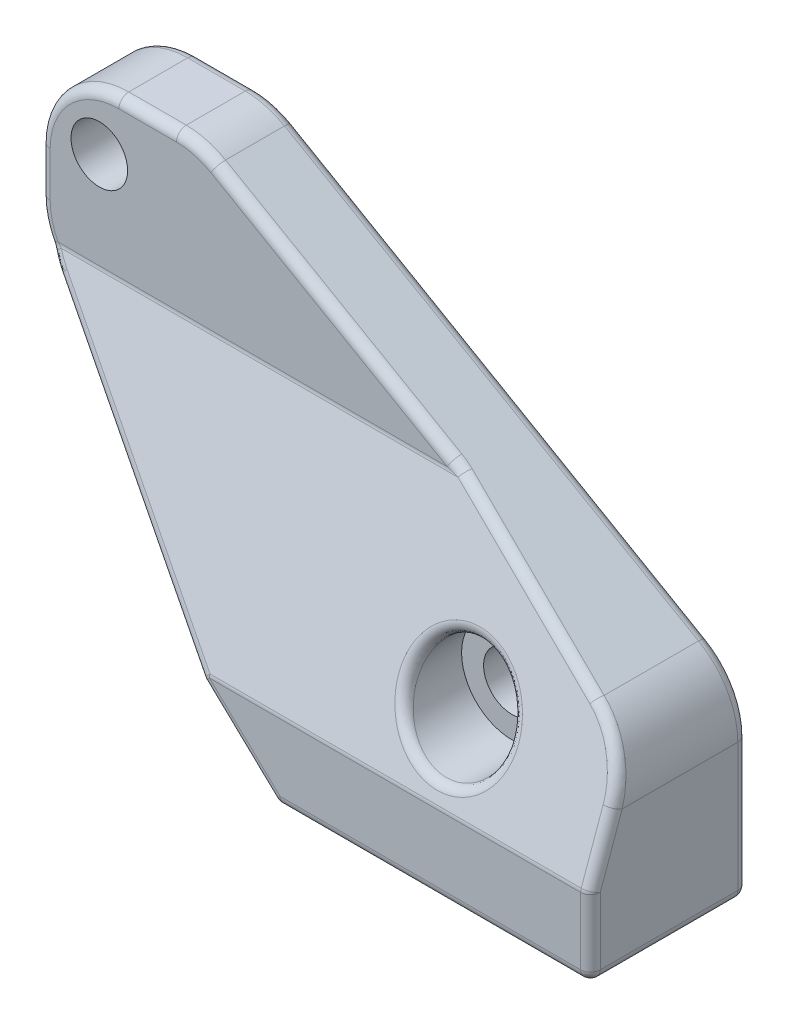
SolidWorks part; units mm, degrees
ref_plane "Front Plane" through (0, 0, 0) normal (0, 0, 1) x (1, 0, 0)
ref_plane "Top Plane" through (0, 0, 0) normal (0, 1, 0) x (1, 0, 0)
ref_plane "Right Plane" through (0, 0, 0) normal (1, 0, 0) x (0, 0, -1)
sketch "Sketch8" plane through (0, 0, 0) normal (0, 0, 1) x (1, 0, 0)
  line L0 (0, 0) -> (-25.4, 0)
  line L3 (-50.8, 36.83) -> (-38.1, 36.83)
  line L4 (-38.1, 36.83) -> (0, 14.833)
  line L5 (0, 14.833) -> (0, 0)
  line L6 (-50.8, 36.83) -> (-50.8, 24.13)
  line L7 (-50.8, 36.83) -> (-50.8, -7.62) construction
  line L8 (-50.8, 24.13) -> (-25.4, 0)
  circle A0 centre (-12.7, 11.8269) radius 2.286 construction
  circle A1 centre (-46.0375, 32.0675) radius 2.286 construction
  circle A2 centre (-12.7, 11.8269) radius 2.286
  circle A3 centre (-46.0375, 32.0675) radius 2.286
  dimension "D1" = 12.7
  dimension "D2" = 12.7
  dimension "D3" = 150
  dimension "D4" = 25.4
extrude "Boss-Extrude1" add sketch "Sketch8" along normal blind 12.7
sketch "Sketch9" plane through (0, 0, 0) normal (0, -1, 0) x (1, 0, 0)
  line L0 (0, 12.7) -> (0, 0) construction
  line L4 (-25.4, 12.7) -> (0, 12.7) construction
  circle A0 centre (-6.35, 6.35) radius 1.905
  circle A1 centre (-19.05, 6.35) radius 1.905
  dimension "D2" = 6.35
  dimension "D4" = 3.81
  dimension "D1" = 6.35
  dimension "D5" = 12.7
  dimension "D3" = 2
extrude "Cut-Extrude4" cut sketch "Sketch9" against normal blind 15.875
sketch "Sketch10" plane through (-50.8, 0, 0) normal (-1, 0, 0) x (0, 0, 1)
  line L0 (6.35, 36.83) -> (6.35, 24.13)
  line L1 (12.7, 36.83) -> (0, 36.83) construction
  line L2 (6.35, 24.13) -> (12.7, 6.35)
  line L3 (12.7, 24.13) -> (12.7, 0) construction
  line L4 (12.7, 6.35) -> (12.7, 36.83)
  line L5 (12.7, 36.83) -> (12.7, 24.13) construction
  line L6 (12.7, 36.83) -> (6.35, 36.83)
  line L7 (12.7, 0) -> (0, 0) construction
  dimension "D1" = 12.7
  dimension "D2" = 6.35
extrude "Cut-Extrude5" cut sketch "Sketch10" against normal through all
sketch "Sketch11" plane through (0, 0, 12.7) normal (0, 0, 1) x (1, 0, 0)
  circle A0 centre (-12.7, 11.8269) radius 4.064
  dimension "D1" = 8.128
extrude "Cut-Extrude6" cut sketch "Sketch11" against normal offset from surface (6.35 mm away) 6.35 up to face at (-10.414, 11.8269, 0)
fillet "Fillet1" radius 6.35 4 edges at (-50.8, 24.13, 3.175) (-50.8, 36.83, 3.175) (-38.1, 36.83, 3.175) (0, 14.833, 4.8352)
fillet "Fillet2" radius 0.7937 29 edges at (-9.639, 20.398, 7.6828) (-0.8507, 14.3418, 9.8458) (-0.8507, 14.3418, 0) (-19.9007, 26.3227, 0) (-38.158, 36.6136, 0) (-42.1257, 36.83, 0) (-48.9401, 34.9701, 0) (-50.8, 28.6681, 0) (-50.285, 24.3511, 0) (-49.5908, 23.1285, 6.7077) (-26.3647, 30.0546, 6.35) (-38.158, 36.6136, 6.35) (-42.1257, 36.83, 6.35) (-48.9401, 34.9701, 6.35) (-50.6444, 25.4588, 6.35) (0, 0, 6.35) (0, 3.175, 12.7) (0, 8.7584, 11.8399) (0, 5.5834, 0) (-28.7421, 3.175, 12.7) (-25.4, 0, 6.35) (-37.1118, 11.1262, 0) (-40.4539, 14.3012, 9.8603) (-12.7, 0, 12.7) (-12.7, 0, 0) (-16.0421, 6.35, 12.7) (-33.144, 24.13, 6.35) (-50.8, 28.6681, 6.35) (-12.7, 7.7629, 12.1954)
